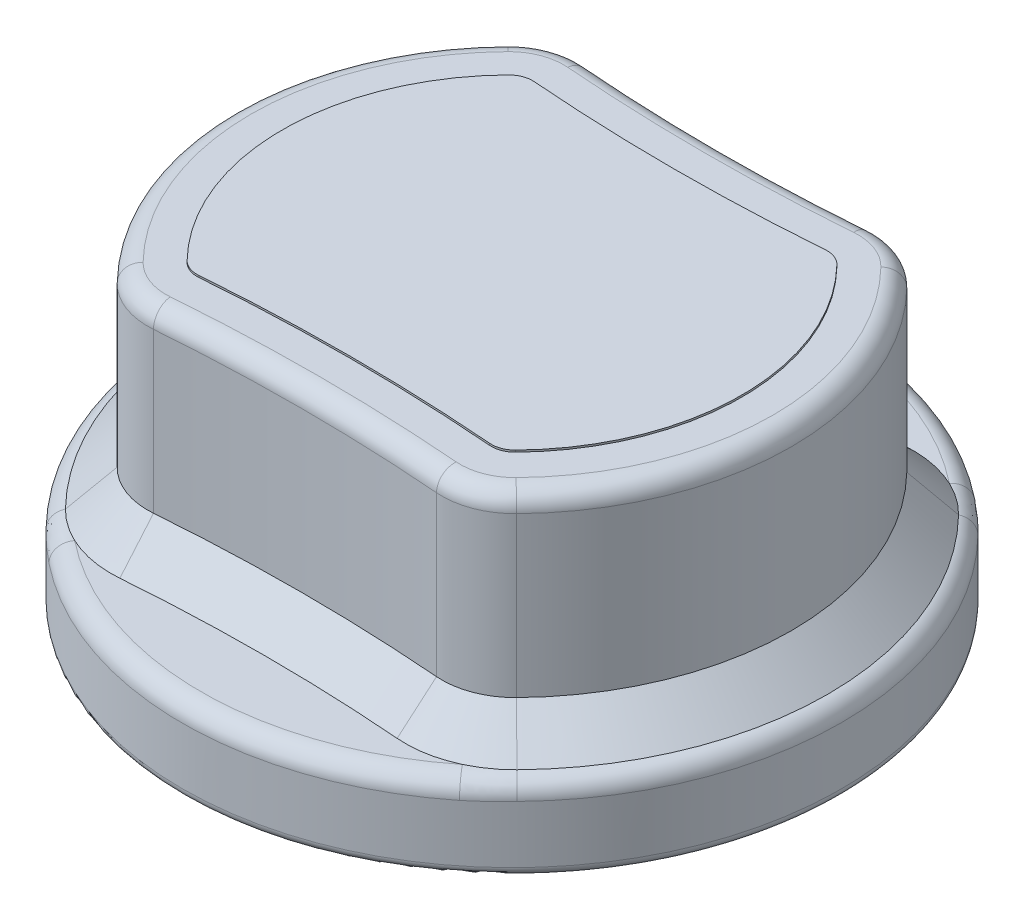
SolidWorks part; units mm, degrees
ref_plane "Ön Düzlem" through (0, 0, 0) normal (0, 0, 1) x (1, 0, 0)
ref_plane "Üst Düzlem" through (0, 0, 0) normal (0, 1, 0) x (1, 0, 0)
ref_plane "Sağ Düzlem" through (0, 0, 0) normal (1, 0, 0) x (0, 0, -1)
sketch "Çizim2" plane through (0, 0, 0) normal (0, 1, 0) x (1, 0, 0)
  circle A0 centre (0, 0) radius 18
  dimension "D1" = 36
extrude "Yükseklik-Ekstrüzyon1" add sketch "Çizim2" along normal blind 4.6
sketch "Çizim3" plane through (0, 4.6, 0) normal (0, 1, 0) x (1, 0, 0)
  line L0 (-9.4108, 12) -> (0, 0) construction
  line L1 (0, 0) -> (-9.4108, -12) construction
  line L2 (0, 18) -> (0, -18) construction
  line L3 (0, 0) -> (9.4108, -12) construction
  line L4 (9.4108, 12) -> (0, 0) construction
  line L5 (-9.4108, 12) -> (-9.4108, -12) construction
  line L6 (-9.4108, 12) -> (9.4108, 12) construction
  line L7 (9.4108, 12) -> (9.4108, -12) construction
  line L8 (9.4108, -12) -> (-9.4108, -12) construction
  line L10 (-15.25, 0) -> (15.25, 0) construction
  arc A0 (-10.9031, 10.6624) -> (-10.9031, -10.6624) centre (0, 0) ccw
  circle A1 centre (0, 0) radius 18 construction
  arc A2 (10.9031, 10.6624) -> (10.9031, -10.6624) centre (0, 0) cw
  arc A3 (-7.7297, 11.8534) -> (7.7297, 11.8534) centre (0, 110.1778) ccw
  arc A4 (-7.7297, -11.8534) -> (7.7297, -11.8534) centre (0, -110.1778) cw
  arc A5 (-10.9031, 10.6624) -> (-7.7297, 11.8534) centre (-8.0432, 7.8657) cw
  arc A6 (7.7297, 11.8534) -> (10.9031, 10.6624) centre (8.0432, 7.8657) cw
  arc A7 (7.7297, -11.8534) -> (10.9031, -10.6624) centre (8.0432, -7.8657) ccw
  arc A8 (-10.9031, -10.6624) -> (-7.7297, -11.8534) centre (-8.0432, -7.8657) ccw
  point P15 (0, 11.55)
  point P33 (0, -11.55)
  dimension "4" = 4
  dimension "D4" = 23.1
  dimension "D2" = 24
  dimension "D3" = 30.5
extrude "Yükseklik-Ekstrüzyon2" add sketch "Çizim3" along normal blind 11.7
chamfer "Pah1" distance 2 angle 45 8 edges at (0, 4.6, 11.55) (9.4488, 4.6, 11.6106) (-9.4488, 4.6, 11.6106) (15.25, 4.6, 0) (-15.25, 4.6, 0) (9.4488, 4.6, -11.6106) (-9.4488, 4.6, -11.6106) (0, 4.6, -11.55)
sketch "Çizim5" plane through (0, 0, 0) normal (0, -1, 0) x (1, 0, 0)
  circle A0 centre (0, 0) radius 16.3
  circle A1 centre (0, 0) radius 18 construction
  dimension "D1" = 1.7
extrude "Kes-Ekstrüzyon2" cut sketch "Çizim5" against normal blind 2.8
sketch "Çizim7" plane through (0, 2.8, 0) normal (0, -1, 0) x (1, 0, 0)
  arc A16 (-9.6876, -9.4738) -> (-7.863, -10.1586) centre (-8.0432, -7.8657) ccw
  arc A17 (-9.6876, 9.4738) -> (-9.6876, -9.4738) centre (0, 0) ccw
  arc A18 (-7.863, 10.1586) -> (-9.6876, 9.4738) centre (-8.0432, 7.8657) ccw
  arc A19 (-7.863, 10.1586) -> (7.863, 10.1586) centre (0, 110.1778) ccw
  arc A20 (9.6876, 9.4738) -> (7.863, 10.1586) centre (8.0432, 7.8657) ccw
  arc A21 (9.6876, -9.4738) -> (9.6876, 9.4738) centre (0, 0) ccw
  arc A22 (7.863, -10.1586) -> (9.6876, -9.4738) centre (8.0432, -7.8657) ccw
  arc A23 (7.863, -10.1586) -> (-7.863, -10.1586) centre (0, -110.1778) ccw
  arc A24 (-9.6876, -9.4738) -> (-7.863, -10.1586) centre (-8.0432, -7.8657) ccw
  arc A25 (-9.6876, 9.4738) -> (-9.6876, -9.4738) centre (0, 0) ccw
  arc A26 (-7.863, 10.1586) -> (-9.6876, 9.4738) centre (-8.0432, 7.8657) ccw
  arc A27 (-7.863, 10.1586) -> (7.863, 10.1586) centre (0, 110.1778) ccw
  arc A28 (9.6876, 9.4738) -> (7.863, 10.1586) centre (8.0432, 7.8657) ccw
  arc A29 (9.6876, -9.4738) -> (9.6876, 9.4738) centre (0, 0) ccw
  arc A30 (7.863, -10.1586) -> (9.6876, -9.4738) centre (8.0432, -7.8657) ccw
  arc A31 (7.863, -10.1586) -> (-7.863, -10.1586) centre (0, -110.1778) ccw
  dimension "D1" = 1.7
extrude "Kes-Ekstrüzyon3" cut sketch "Çizim7" against normal blind 10.7
chamfer "Pah2" distance 2 angle 45 8 edges at (-13.55, 2.8, 0) (-8.8514, 2.8, -10.019) (-8.8514, 2.8, 10.019) (0, 2.8, -9.85) (0, 2.8, 9.85) (8.8514, 2.8, -10.019) (8.8514, 2.8, 10.019) (13.55, 2.8, 0)
sketch "Çizim4" plane through (0, 16.3, 0) normal (0, 1, 0) x (1, 0, 0)
  arc A16 (-7.9414, 9.1617) -> (-8.9727, 8.7746) centre (-8.0432, 7.8657) ccw
  arc A17 (-8.9727, 8.7746) -> (-8.9727, -8.7746) centre (0, 0) ccw
  arc A18 (-8.9727, -8.7746) -> (-7.9414, -9.1617) centre (-8.0432, -7.8657) ccw
  arc A19 (7.9414, -9.1617) -> (-7.9414, -9.1617) centre (0, -110.1778) ccw
  arc A20 (7.9414, -9.1617) -> (8.9727, -8.7746) centre (8.0432, -7.8657) ccw
  arc A21 (8.9727, -8.7746) -> (8.9727, 8.7746) centre (0, 0) ccw
  arc A22 (8.9727, 8.7746) -> (7.9414, 9.1617) centre (8.0432, 7.8657) ccw
  arc A23 (-7.9414, 9.1617) -> (7.9414, 9.1617) centre (0, 110.1778) ccw
  arc A24 (-7.9414, 9.1617) -> (-8.9727, 8.7746) centre (-8.0432, 7.8657) ccw
  arc A25 (-8.9727, 8.7746) -> (-8.9727, -8.7746) centre (0, 0) ccw
  arc A26 (-8.9727, -8.7746) -> (-7.9414, -9.1617) centre (-8.0432, -7.8657) ccw
  arc A27 (7.9414, -9.1617) -> (-7.9414, -9.1617) centre (0, -110.1778) ccw
  arc A28 (7.9414, -9.1617) -> (8.9727, -8.7746) centre (8.0432, -7.8657) ccw
  arc A29 (8.9727, -8.7746) -> (8.9727, 8.7746) centre (0, 0) ccw
  arc A30 (8.9727, 8.7746) -> (7.9414, 9.1617) centre (8.0432, 7.8657) ccw
  arc A31 (-7.9414, 9.1617) -> (7.9414, 9.1617) centre (0, 110.1778) ccw
  dimension "D1" = 2.7
fillet "Radyus4" radius 1 8 edges at (0, 16.3, -11.55) (9.4488, 16.3, -11.6106) (15.25, 16.3, 0) (9.4488, 16.3, 11.6106) (0, 16.3, 11.55) (-9.4488, 16.3, 11.6106) (-15.25, 16.3, 0) (-9.4488, 16.3, -11.6106)
fillet "Radyus5" radius 1 1 edges at (0, 4.6, 18)
sketch "Çizim9" plane through (0, 13.5, 0) normal (0, -1, 0) x (1, 0, 0)
  circle A0 centre (0, 0) radius 4.4
  circle A1 centre (0, 0) radius 2.4
  dimension "D1" = 8.8
  dimension "D2" = 2
extrude "Yükseklik-Ekstrüzyon3" add sketch "Çizim9" along normal blind 14.65
ref_plane "Düzlem1" through (6.1, 0, 0) normal (1, 0, 0) x (0, 0, -1)
fillet "Radyus6" radius 0.5 3 edges at (0, 0, 18) (0, 0, -16.3) (0, 2.8, -16.3)
fillet "Radyus7" radius 1 8 edges at (-9.5542, 2.8, 11.8915) (-15.55, 2.8, 0) (-9.5542, 2.8, -11.8915) (0, 2.8, -11.85) (9.5542, 2.8, -11.8915) (15.55, 2.8, 0) (9.5542, 2.8, 11.8915) (0, 2.8, 11.85)
fillet "Radyus8" radius 1 9 edges at (-8.8514, 13.5, 10.019) (0, 13.5, 9.85) (8.8514, 13.5, 10.019) (13.55, 13.5, 0) (8.8514, 13.5, -10.019) (0, 13.5, -9.85) (-8.8514, 13.5, -10.019) (-13.55, 13.5, 0) (0, 13.5, -4.4)
ref_plane "Düzlem2" through (0, 0, 0) normal (0, 0, 1) x (1, 0, 0)
sketch "Çizim13" plane through (0, 0, 0) normal (0, 0, 1) x (1, 0, 0)
  line L0 (-4.4, 5.6306) -> (-7.5, 4.8)
  line L1 (-4.4, 12.5) -> (-4.4, -1.15) construction
  line L3 (-7.5, 4.8) -> (-7.5, 3.17)
  line L4 (-7.5, 3.17) -> (-4.4, 3.17)
  line L6 (-7.9414, 13.5) -> (7.9414, 13.5) construction
  line L7 (4.4, 5.6306) -> (6.1, 4.8)
  line L8 (4.4, -1.15) -> (4.4, 12.5) construction
  line L9 (6.1, 4.8) -> (6.1, 3.17)
  line L10 (6.1, 3.17) -> (4.4, 3.17)
  line L12 (-4.4, 5.6306) -> (-3.0456, 5.9831)
  line L13 (-3.0456, 5.9831) -> (-3.0456, 3.17)
  line L14 (-3.0456, 3.17) -> (-4.4, 3.17)
  line L15 (4.4, 3.17) -> (2.9854, 3.17)
  line L16 (2.9854, 3.17) -> (2.9854, 6.3218)
  line L17 (2.9854, 6.3218) -> (4.4, 5.6306)
  dimension "D1" = 8.7
  dimension "D3" = 1.63
  dimension "D4" = 3.1
  dimension "D5" = 1.7
extrude "Yükseklik-Ekstrüzyon18" add sketch "Çizim13" along normal blind 1.625 and the other way blind 1.625 separate body
sketch "Çizim10" plane through (6.1, 0, 0) normal (1, 0, 0) x (0, 0, -1)
  circle A0 centre (0, 3.1746) radius 1.625
  dimension "D1" = 3.25
extrude "Yükseklik-Ekstrüzyon4" add sketch "Çizim10" against normal blind 13.58 from offset 0.01
sketch "Çizim11" plane through (0, -1.15, 0) normal (0, -1, 0) x (1, 0, 0)
  circle A0 centre (0, 0) radius 2.4
extrude "Kes-Ekstrüzyon4" cut sketch "Çizim11" against normal blind 13.6
extrude "Yükseklik-Ekstrüzyon19" add sketch "Çizim4" along normal blind 0.1
